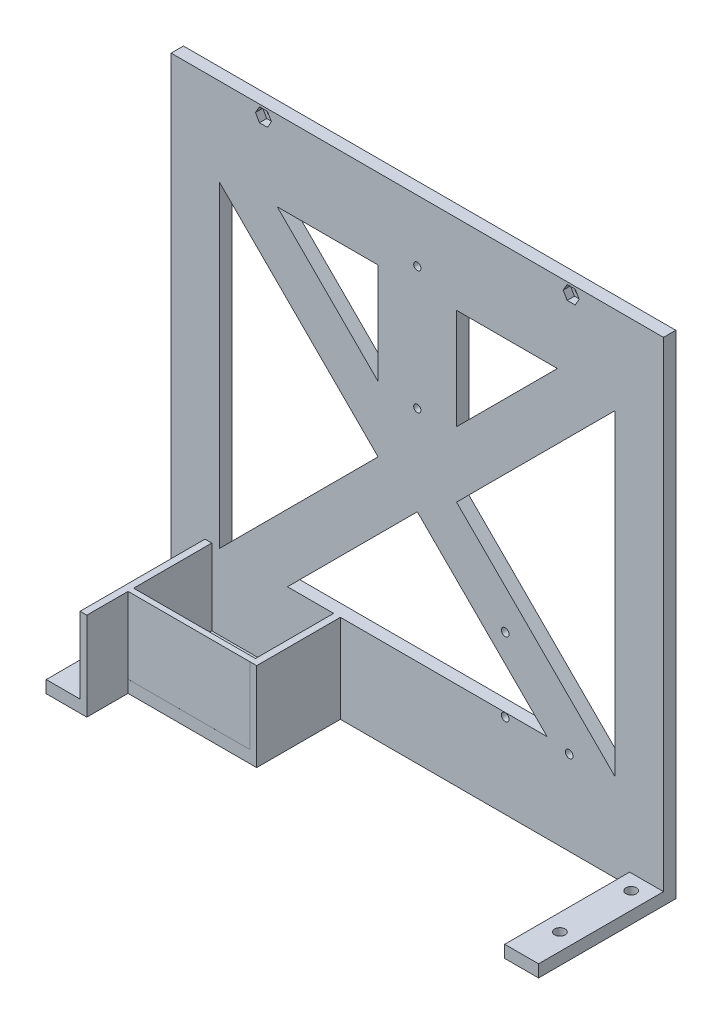
SolidWorks part; units mm, degrees
ref_plane "Front" through (0, 0, 0) normal (0, 0, 1) x (1, 0, 0)
ref_plane "Top" through (0, 0, 0) normal (0, 1, 0) x (1, 0, 0)
ref_plane "Right" through (0, 0, 0) normal (1, 0, 0) x (0, 0, -1)
sketch "Sketch1" plane through (0, 0, 0) normal (0, 0, 1) x (1, 0, 0)
  line L0 (-81.5432, 65.3545) -> (-81.5432, -65.3545)
  line L1 (-101.6, 101.6) -> (101.6, 101.6)
  line L2 (-101.6, 101.6) -> (-101.6, -101.6)
  line L3 (-101.6, -101.6) -> (101.6, -101.6)
  line L4 (101.6, 101.6) -> (101.6, -101.6)
  line L5 (-101.6, 101.6) -> (101.6, -101.6) construction
  line L6 (-101.6, -101.6) -> (101.6, 101.6) construction
  line L7 (0, -55) -> (0, 55) construction
  line L8 (-81.5432, -65.3545) -> (-16.1887, 0)
  line L9 (-16.1887, 0) -> (-81.5432, 65.3545)
  line L10 (55, 0) -> (-55, 0) construction
  line L11 (16.1887, 0) -> (81.5432, 65.3545)
  line L12 (81.5432, -65.3545) -> (16.1887, 0)
  line L13 (81.5432, 65.3545) -> (81.5432, -65.3545)
  line L14 (-16.1887, 68.5673) -> (-16.1887, 26.9408)
  line L15 (-16.1887, 26.9408) -> (-57.8152, 68.5673)
  line L16 (-57.8152, 68.5673) -> (-16.1887, 68.5673)
  line L17 (16.1887, 26.9408) -> (57.8152, 68.5673)
  line L18 (16.1887, 68.5673) -> (16.1887, 26.9408)
  line L19 (57.8152, 68.5673) -> (16.1887, 68.5673)
  line L20 (-53.5883, -65.1346) -> (0, -11.5463)
  line L21 (0, -11.5463) -> (53.5883, -65.1346)
  line L22 (53.5883, -65.1346) -> (-53.5883, -65.1346)
  circle A0 centre (0, 76.2) radius 1.5
  circle A2 centre (0, 25.4) radius 1.5
  circle A3 centre (-63.5, 97.79) radius 1.5
  circle A4 centre (63.5, 97.79) radius 1.5
  point P0 (0, 0)
  dimension "D3" = 3
  dimension "D4" = 50.8
  dimension "D6" = 19.05
  dimension "D7" = 3
  dimension "D9" = 63.5
  dimension "D1" = 203.2
  dimension "D2" = 203.2
  dimension "D5" = 25.4
  dimension "D8" = 3.81
extrude "Boss-Extrude1" add sketch "Sketch1" along normal blind 5.08 contours L4 L1 L2 L3 A2 A0 L19 L17 L18 L9 L8 L0 L11 L13 L12 L15 L16 L14 L21 L22 L20 region at (0, 1.383, 0)
sketch "Sketch2" plane through (0, 0, 5.08) normal (0, 0, 1) x (1, 0, 0)
  line L0 (-101.6, -101.6) -> (101.6, -101.6) construction
  line L1 (-101.6, -101.6) -> (-87.63, -101.6)
  line L2 (-101.6, -101.6) -> (-101.6, -96.52)
  line L3 (-101.6, -96.52) -> (-87.63, -96.52)
  line L4 (-87.63, -101.6) -> (-87.63, -96.52)
  line L5 (0, -55) -> (0, 55) construction
  line L6 (101.6, -96.52) -> (87.63, -96.52)
  line L7 (87.63, -101.6) -> (87.63, -96.52)
  line L8 (101.6, -101.6) -> (87.63, -101.6)
  line L9 (101.6, -101.6) -> (101.6, -96.52)
  line L10 (53.5883, -65.1346) -> (-53.5883, -65.1346) construction
  line L11 (-87.63, -96.52) -> (-31.75, -96.52)
  line L12 (-87.63, -96.52) -> (-87.63, -101.6)
  line L13 (-87.63, -101.6) -> (-31.75, -101.6)
  line L14 (-31.75, -96.52) -> (-31.75, -101.6)
  line L15 (-87.63, -96.52) -> (-84.836, -96.52)
  line L16 (-87.63, -96.52) -> (-87.63, -65.1346)
  line L17 (-87.63, -65.1346) -> (-84.836, -65.1346)
  line L18 (-84.836, -96.52) -> (-84.836, -65.1346)
  line L19 (-31.75, -96.52) -> (-34.544, -96.52)
  line L20 (-31.75, -96.52) -> (-31.75, -65.1346)
  line L21 (-31.75, -65.1346) -> (-34.544, -65.1346)
  line L22 (-34.544, -96.52) -> (-34.544, -65.1346)
  line M10 (-101.6, -101.6) -> (101.6, -101.6)
  dimension "D1" = 5.08
  dimension "D2" = 55.88
  dimension "D3" = 50.292
  dimension "D4" = 13.97
  dimension "D5" = 31.75
extrude "Boss-Extrude2" add sketch "Sketch2" along normal blind 51.562 contours L4 L3 L2 M10 | L14 L11 L4 M10 | L9 L6 L7 M10 | L16 L15 L18 L17 | L20 L19 L22 L21 region at (-94.615, -99.06, 5.08) region at (94.615, -99.06, 5.08) region at (-59.69, -99.06, 5.08)
sketch "Sketch3" plane through (0, -96.52, 0) normal (0, 1, 0) x (1, 0, 0)
  line L4 (0, -55) -> (0, 55) construction
  line L10 (-101.6, -5.08) -> (-87.63, -5.08) construction
  line L11 (-101.6, -56.642) -> (-101.6, -5.08) construction
  circle A0 centre (-94.615, -11.43) radius 2.159
  circle A1 centre (94.615, -11.43) radius 2.159
  circle A2 centre (-94.615, -40.84) radius 2.159
  circle A3 centre (94.615, -40.84) radius 2.159
  dimension "D1" = 4.318
  dimension "D4" = 29.41
  dimension "D5" = 4.318
  dimension "D6" = 4.318
  dimension "D2" = 6.35
  dimension "D3" = 6.985
extrude "Cut-Extrude1" cut sketch "Sketch3" against normal up to next contours A0 | A1 | A3 | A2 | A2 | A3 region at (-94.615, -96.52, 11.43) region at (94.615, -96.52, 11.43) region at (-94.615, -96.52, 40.84) region at (94.615, -96.52, 40.84)
sketch "Sketch7" plane through (0, 0, 5.08) normal (0, 0, 1) x (1, 0, 0)
  circle A0 centre (36.2876, -66.7853) radius 1.5875
  circle A1 centre (36.2876, -36.4323) radius 1.5875
  circle A3 centre (62.7036, -66.7853) radius 1.5875
  dimension "D1" = 3.175
  dimension "D2" = 30.353
  dimension "D3" = 26.416
extrude "Cut-Extrude2" cut sketch "Sketch7" against normal up to next
sketch "Sketch8" plane through (-34.544, 0, 0) normal (-1, 0, 0) x (0, 0, 1)
  line L0 (56.642, -65.1346) -> (5.08, -65.1346) construction
  line L1 (37.33, -65.1346) -> (39.63, -65.1346)
  line L2 (37.33, -65.1346) -> (37.33, -96.52)
  line L3 (37.33, -96.52) -> (39.63, -96.52)
  line L4 (39.63, -65.1346) -> (39.63, -96.52)
  line L5 (56.642, -96.52) -> (5.08, -96.52) construction
  line L7 (5.08, -96.52) -> (5.08, -65.1346) construction
  dimension "D1" = 2.3
  dimension "D2" = 32.25
extrude "Boss-Extrude6" add sketch "Sketch8" along normal up to next
sketch "Sketch10" plane through (-31.75, 0, 0) normal (1, 0, 0) x (0, 0, -1)
  line L0 (-56.642, -65.1346) -> (-5.08, -65.1346) construction
  line L1 (-56.642, -101.6) -> (-39.632, -101.6)
  line L2 (-56.642, -101.6) -> (-56.642, -65.1346)
  line L3 (-56.642, -65.1346) -> (-39.632, -65.1346)
  line L4 (-39.632, -101.6) -> (-39.632, -65.1346)
  point P7 (-56.642, -83.3673)
  dimension "D1" = 17.01
extrude "Cut-Extrude3" cut sketch "Sketch10" against normal blind 53.09
sketch "Sketch11" plane through (0, 0, 5.08) normal (0, 0, 1) x (1, 0, 0)
  line L0 (0, -31.1531) -> (0, 31.1531) construction
  line L1 (-61.8546, 94.94) -> (-60.2091, 97.79)
  line L2 (-60.2091, 97.79) -> (-61.8546, 100.64)
  line L3 (-61.8546, 100.64) -> (-65.1454, 100.64)
  line L4 (-65.1454, 100.64) -> (-66.7909, 97.79)
  line L5 (-66.7909, 97.79) -> (-65.1454, 94.94)
  line L6 (-65.1454, 94.94) -> (-61.8546, 94.94)
  line L7 (65.1454, 94.94) -> (61.8546, 94.94)
  line L8 (66.7909, 97.79) -> (65.1454, 94.94)
  line L9 (65.1454, 100.64) -> (66.7909, 97.79)
  line L10 (61.8546, 100.64) -> (65.1454, 100.64)
  line L11 (60.2091, 97.79) -> (61.8546, 100.64)
  line L12 (61.8546, 94.94) -> (60.2091, 97.79)
  circle A0 centre (-63.5, 97.79) radius 1.5 construction
  circle A1 centre (-63.5, 97.79) radius 1.5
  circle A2 centre (-63.5, 97.79) radius 2.85 construction
  circle A3 centre (63.5, 97.79) radius 2.85 construction
  circle A4 centre (63.5, 97.79) radius 1.5
  circle M36 centre (-63.5, 97.79) radius 1.5
  circle M37 centre (63.5, 97.79) radius 1.5
  dimension "D1" = 5.7
extrude "Cut-Extrude4" cut sketch "Sketch11" against normal blind 3 contours L5 L6 L1 L2 L3 L4 M36 | L12 L7 L8 L9 L10 L11 M37 region at (-63.5, 95.0271, 5.08) region at (63.5, 95.0271, 5.08)
